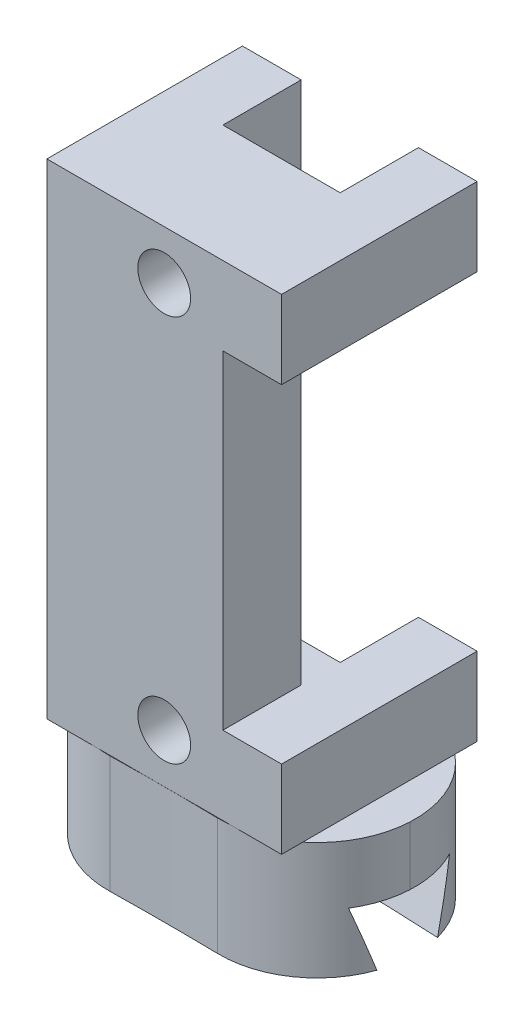
SolidWorks part; units mm, degrees
ref_plane "Front Plane" through (0, 0, 0) normal (0, 0, 1) x (1, 0, 0)
ref_plane "Top Plane" through (0, 0, 0) normal (0, 1, 0) x (1, 0, 0)
ref_plane "Right Plane" through (0, 0, 0) normal (1, 0, 0) x (0, 0, -1)
ref_axis "Axis2" through (0, 11, 0) along (0, -1, 0)
ref_plane "Plane2" through (0, 0, -150) normal (0, 0, 1) x (1, 0, 0)
sketch "Sketch7" plane through (0, 0, -150) normal (0, 0, 1) x (1, 0, 0)
  line L1 (-6, 24.8) -> (6, 24.8)
  line L2 (-6, 24.8) -> (-6, 0)
  line L4 (6, 24.8) -> (6, 0)
  line L7 (-6, 0) -> (6, 0)
  point P4 (12.4, 0)
  point P6 (6, 0)
  point P8 (0, 0)
  point P11 (0, 24.8)
  dimension "D1" = 24.8
  dimension "D2" = 12
extrude "Main" add sketch "Sketch7" along normal mid plane 10
sketch "Sketch8" plane through (0, 0, -145) normal (0, 0, 1) x (1, 0, 0)
  line L1 (-6, 24.8) -> (-6, 0) construction
  line L2 (6, 24.8) -> (-6, 24.8) construction
  circle A0 centre (0, 22.3) radius 1.35
  circle A1 centre (0, 2.5) radius 1.35
  point P4 (16.3, 0.5257)
  point P5 (0, 0)
  point P6 (-3.5, 21.128)
  dimension "D1" = 2.7
  dimension "D2" = 2.5
  dimension "D3" = 19.8
  dimension "D4" = 6
extrude "Holes" cut sketch "Sketch8" against normal through all
sketch "Sketch9" plane through (0, 0, -145) normal (0, 0, 1) x (1, 0, 0)
  line L1 (6, 24.8) -> (-6, 24.8)
  line L2 (6, 24.8) -> (6, 12.8)
  line L3 (6, 12.8) -> (-6, 12.8)
  line L4 (-6, 24.8) -> (-6, 12.8)
  dimension "D3" = 12
sketch "Sketch16" plane through (6, 0, 0) normal (1, 0, 0) x (0, 0, -1)
  line L1 (149, 20.8) -> (155, 20.8)
  line L2 (149, 20.8) -> (149, 4)
  line L3 (149, 4) -> (155, 4)
  line L4 (155, 20.8) -> (155, 4)
  line L5 (155, 0) -> (155, 24.8) construction
  dimension "D1" = 6
  dimension "D2" = 4
  dimension "D3" = 4
extrude "FixExtrusion" cut sketch "Sketch16" against normal through all
sketch "Sketch10" plane through (0, 0, 0) normal (1, 0, 0) x (0, 0, -1)
  line L0 (152.5, -3) -> (147.5, -3)
  line L1 (152.5, -3) -> (151.5, -6)
  line L3 (151.5, -6) -> (155, -6)
  line L4 (155, -6) -> (155, 0)
  line L5 (155, 0) -> (145, 0)
  line L6 (145, 0) -> (145, -6)
  line L7 (147.5, -3) -> (148.5, -6)
  line L9 (148.5, -6) -> (145, -6)
  line L10 (145, 0) -> (155, 0) construction
  point P2 (149.3463, -7)
  point P9 (150, 0)
  point P11 (-151.5, -8.4076)
  point P12 (150, -3)
  point P15 (-123.865, 0)
  point P16 (0, 0)
  point P19 (149.4644, -7)
  dimension "D1" = 3
  dimension "D3" = 5
  dimension "D5" = 3
  dimension "D6" = 6
  dimension "D7" = 150
  dimension "D9" = 3.5
revolve "Support" add sketch "Sketch10" angle 6 mid plane about axis through (0, 11, 0) along (0, -1, 0)
fillet "Fillet1" radius 5 4 edges at (8.1121, -3, -154.7876) (-8.1121, -3, -154.7876) (7.5887, -3, -144.8013) (-7.5887, -3, -144.8013)
sketch "Sketch17" plane through (0, 0, -155) normal (0, 0, -1) x (-1, 0, 0)
  line L0 (-6, 24.8) -> (6, 24.8) construction
  line L1 (-3, 24.8) -> (3, 24.8)
  line L2 (-3, 24.8) -> (-3, 0)
  line L3 (-3, 0) -> (3, 0)
  line L4 (3, 24.8) -> (3, 0)
  line L5 (6, 0) -> (-6, 0) construction
  line L6 (-6, 20.8) -> (-6, 24.8) construction
  dimension "D1" = 6
  dimension "D2" = 3
extrude "Cut-Extrude1" cut sketch "Sketch17" against normal blind 4
sketch "Sketch18" plane through (0, 0, -149) normal (0, 0, -1) x (-1, 0, 0)
  line L0 (6, 4) -> (-6, 4) construction
  line L1 (-6, 20.8) -> (-3, 20.8)
  line L2 (-6, 20.8) -> (-6, 4)
  line L3 (-6, 4) -> (-3, 4)
  line L4 (-3, 20.8) -> (-3, 4)
  point P7 (0, 0)
  dimension "D1" = 3
extrude "Cut-Extrude2" cut sketch "Sketch18" against normal through all
